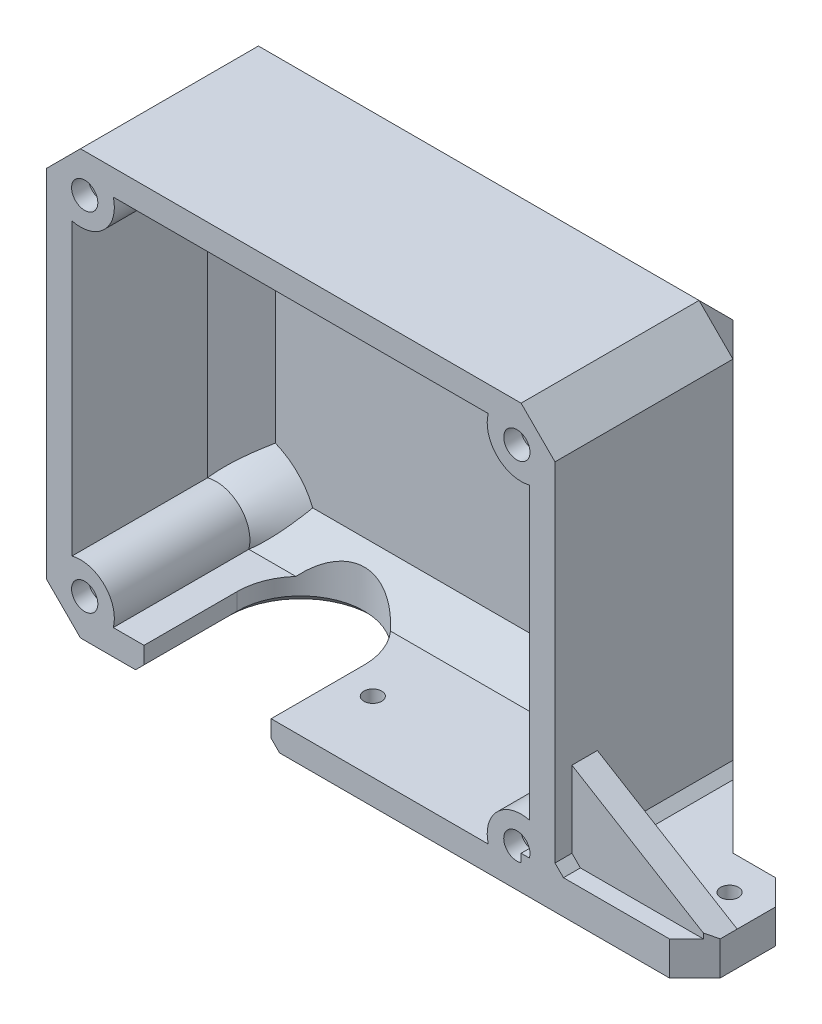
SolidWorks part; units mm, degrees
ref_plane "Front Plane" through (0, 0, 0) normal (0, 0, 1) x (1, 0, 0)
ref_plane "Top Plane" through (0, 0, 0) normal (0, 1, 0) x (1, 0, 0)
ref_plane "Right Plane" through (0, 0, 0) normal (1, 0, 0) x (0, 0, -1)
sketch "Sketch1" plane through (0, 0, 0) normal (0, 0, 1) x (1, 0, 0)
  line L0 (0, 0) -> (0, 50)
  line L1 (0, 50) -> (60, 50)
  line L2 (60, 50) -> (60, 0)
  line L3 (60, 0) -> (0, 0)
extrude "Boss-Extrude1" add sketch "Sketch1" along normal blind 5
sketch "Sketch2" plane through (0, 0, 5) normal (0, 0, 1) x (1, 0, 0)
  line L0 (60, 50) -> (0, 50) construction
  line L1 (0, 50) -> (0, 0) construction
  line L2 (60, 0) -> (60, 50) construction
  line L3 (3, 25) -> (57, 25) construction
  line L8 (57, 3) -> (57, 47)
  line L9 (3, 3) -> (57, 3)
  line L10 (3, 47) -> (3, 3)
  line L11 (57, 47) -> (3, 47)
  line L12 (57, 3) -> (57, 47)
  line L13 (3, 3) -> (57, 3)
  line L14 (3, 47) -> (3, 3)
  line L15 (57, 47) -> (3, 47)
  circle A0 centre (4, 46) radius 4
  circle A1 centre (56, 46) radius 4
  circle A2 centre (56, 4) radius 4
  circle A3 centre (4, 4) radius 4
  line M5 (0, 0) -> (60, 0)
  line M6 (60, 0) -> (60, 50)
  line M7 (60, 50) -> (0, 50)
  line M8 (0, 50) -> (0, 0)
  dimension "D2" = 8
  dimension "D3" = 8
  dimension "D4" = 4
  dimension "D5" = 4
  dimension "D6" = 4
  dimension "D7" = 4
  dimension "D1" = 3
extrude "Boss-Extrude2" add sketch "Sketch2" along normal blind 20 contours A1 A0 L15 M7 | A0 M7 M8 | L15 A0 L14 | A3 L14 A0 M8 | L14 A0 L15 | A3 L13 L14 | A3 M5 M8 | L13 A3 A2 M5 | A3 L14 L13 | A2 L12 L13 | A2 M6 M5 | A2 L13 L12 | L12 A2 A1 M6 | A1 M6 M7 | A1 L15 L12 | L15 A1 L12
chamfer "Chamfer1" distance 4 angle 45 8 edges at (30, 3, 5) (6.8284, 43.1716, 5) (3, 25, 5) (30, 47, 5) (53.1716, 43.1716, 5) (57, 25, 5) (53.1716, 6.8284, 5) (6.8284, 6.8284, 5)
chamfer "Chamfer2" distance 4 angle 45 8 edges at (60, 25, 0) (60, 50, 12.5) (30, 50, 0) (0, 50, 12.5) (0, 25, 0) (60, 0, 12.5) (30, 0, 0) (0, 0, 12.5)
sketch "Sketch3" plane through (0, 0, 0) normal (0, -1, 0) x (1, 0, 0)
  line L0 (4, 25) -> (4, 4) construction
  line L1 (4, 4) -> (56, 4) construction
  line L2 (11.5, 14) -> (11.5, 25)
  line L3 (4, 25) -> (56, 25) construction
  line L4 (26.5, 14) -> (26.5, 25)
  line L5 (26.5, 25) -> (11.5, 25)
  circle A0 centre (19, 14) radius 7.5
  line M3 (56, 25) -> (4, 25)
  dimension "D1" = 15
  dimension "D2" = 15
  dimension "D3" = 10
extrude "Cut-Extrude1" cut sketch "Sketch3" against normal up to next contours A0 L4 L2 M3 | A0
sketch "Sketch5" plane through (0, 0, 25) normal (0, 0, 1) x (1, 0, 0)
  line L0 (0, 25) -> (60, 25) construction
  line L1 (0, 46) -> (0, 4) construction
  line L2 (60, 4) -> (60, 46) construction
  line L3 (56, 50) -> (4, 50) construction
  circle A0 centre (4.5, 45.5) radius 1.55
  circle A1 centre (55.5, 45.5) radius 1.55
  circle A2 centre (55.5, 4.5) radius 1.55
  circle A3 centre (4.5, 4.5) radius 1.55
  dimension "D1" = 3.1
  dimension "D2" = 3.1
  dimension "D3" = 4.5
  dimension "D4" = 4.5
  dimension "D5" = 4.5
  dimension "D6" = 4.5
extrude "Cut-Extrude2" cut sketch "Sketch5" against normal blind 2
chamfer "Chamfer3" distance 1 angle 45 3 edges at (26.5, 0, 19.5) (11.5, 0, 19.5) (19, 0, 6.5)
sketch "Sketch6" plane through (0, 0, 0) normal (0, -1, 0) x (1, 0, 0)
  line L0 (60, 25) -> (60, 4) construction
  line L1 (60, 4) -> (56, 0) construction
  line L2 (60, 25) -> (60, 4)
  line L3 (60, 4) -> (56, 0)
  line L4 (60, 4) -> (68.4853, 12.4853)
  line L5 (68.4853, 12.4853) -> (76.5, 12.4853)
  line L6 (66.5, 11) -> (66.5, 54) construction
  line L10 (76.5, 12.4853) -> (76.5, 25)
  line L11 (76.5, 25) -> (60, 25)
  line L12 (56, 0) -> (56, 25)
  line L13 (56, 25) -> (60, 25)
  dimension "D1" = 12
  dimension "D2" = 10
extrude "Boss-Extrude3" add sketch "Sketch6" against normal blind 4
sketch "Sketch7" plane through (56, 0, 0) normal (-1, 0, 0) x (0, 0, 1)
  line L3 (4, 0) -> (0, 4)
  line L4 (0, 4) -> (0, 0)
  line L5 (0, 0) -> (4, 0)
  line L6 (4, 0) -> (0, 4)
  line L7 (0, 4) -> (0, 0)
  line L8 (0, 0) -> (4, 0)
  dimension "D1" = 0
extrude "Cut-Extrude3" cut sketch "Sketch7" against normal up to next
ref_plane "Plane1" through (0, 0, 23) normal (0, 0, 1) x (1, 0, 0)
sketch "Sketch10" plane through (0, 0, 0) normal (0, -1, 0) x (1, 0, 0)
  circle A0 centre (72.3, 16.7) radius 1.05 construction
  circle A1 centre (30.2, 16.7) radius 1.05 construction
  circle A2 centre (72.3, 16.7) radius 1.05
  circle A3 centre (30.2, 16.7) radius 1.05
extrude "Cut-Extrude5" cut sketch "Sketch10" against normal up to next
sketch "Sketch11" plane through (0, 0, 23) normal (0, 0, 1) x (1, 0, 0)
  line L0 (76.5, 4) -> (60, 4) construction
  line L1 (60, 4) -> (60, 46) construction
  line L2 (76.5, 4) -> (60, 4)
  line L3 (60, 4) -> (60, 46)
  line L4 (76.5, 4) -> (60, 14)
  line L5 (60, 14) -> (59, 14)
  line L6 (76.5, 4) -> (76.5, 3)
  line L7 (76.5, 3) -> (59, 3)
  line L8 (59, 3) -> (59, 14)
  dimension "D1" = 10
  dimension "D2" = 1
  dimension "D3" = 1
extrude "Boss-Extrude5" add sketch "Sketch11" against normal blind 3 contours L8 L7 L6 L2 L3 L5 | L2 L4 L3
chamfer "Chamfer6" distance 1 angle 45 1 edges at (60, 4, 24)
chamfer "Chamfer7" distance 3 angle 45 2 edges at (76.5, 2, 25) (76.5, 2, 12.4853)
